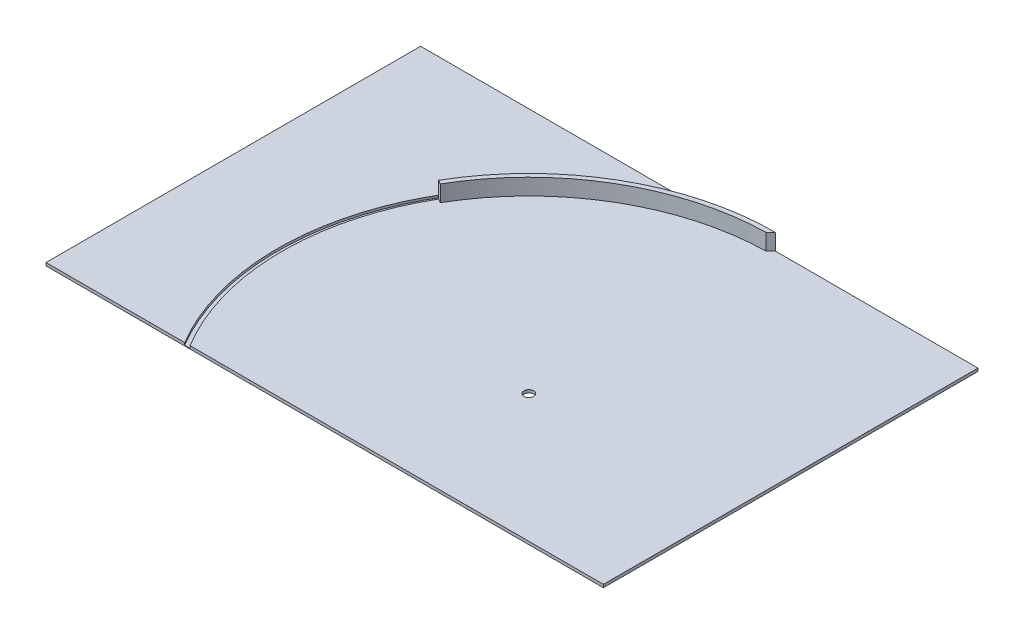
SolidWorks part; units mm, degrees
ref_plane "Front Plane" through (0, 0, 0) normal (0, 0, 1) x (1, 0, 0)
ref_plane "Top Plane" through (0, 0, 0) normal (0, 1, 0) x (1, 0, 0)
ref_plane "Right Plane" through (0, 0, 0) normal (1, 0, 0) x (0, 0, -1)
sketch "Sketch3" plane through (0, 0, 0) normal (0, 1, 0) x (1, 0, 0)
  line L1 (0, 0) -> (-839.8654, 0) construction
  line L2 (0, 0) -> (-451.1992, 260.5) construction
  line L3 (0, 531) -> (0, 521)
  line L4 (-459.8595, 265.5) -> (-451.1992, 260.5)
  circle A0 centre (0, 0) radius 250 construction
  arc A1 (0, 521) -> (-451.1992, 260.5) centre (0, 0) ccw
  arc A2 (0, 531) -> (-459.8595, 265.5) centre (0, 0) ccw
  dimension "D1" = 500
  dimension "D2" = 521
  dimension "D3" = 30
  dimension "D4" = 10
extrude "Boss-Extrude1" add sketch "Sketch3" along normal blind 35
sketch "Sketch4" plane through (0, 0, 0) normal (0, 1, 0) x (1, 0, 0)
  line L1 (-764.07, -275.4) -> (435.93, -275.4)
  line L2 (-764.07, -275.4) -> (-764.07, 531)
  line L3 (-764.07, 531) -> (435.93, 531)
  line L4 (435.93, -275.4) -> (435.93, 531)
  arc A0 (0, 531) -> (-459.8595, 265.5) centre (0, 0) ccw construction
  dimension "D1" = 1200
  dimension "D2" = 275.4
  dimension "D3" = 764.07
extrude "Boss-Extrude2" add sketch "Sketch4" against normal blind 6.35
chamfer "Chamfer1" distance 10 angle 45 1 edges at (0, 17.5, -521)
hole_wizard "Ø20.0mm Dowel Hole1" positions "Sketch6" profile "Sketch7" hole size "Ø20.0" standard "ANSI Metric" end condition through all
sketch "Sketch6" plane through (0, 0, 0) normal (0, 1, 0) x (1, 0, 0)
  point P0 (0, 0)
sketch "Sketch7" plane through (0, 0, 0) normal (1, 0, 0) x (0, 0, 1)
  line L0 (0, 0) -> (0, 6.35)
  line L1 (0, 6.35) -> (10.5, 6.35)
  line L2 (10.5, 6.35) -> (10.5, 0)
  line L5 (10.5, 0) -> (0, 0)
  line L11 (0, -6.35) -> (0, 107.95) construction
  dimension "Thru Hole Dia." = 21
  dimension "Thru Hole Depth" = 6.35
sketch "Sketch8" plane through (0, 0, 0) normal (0, 1, 0) x (1, 0, 0)
  line L1 (0, 531) -> (-764.07, 531) construction
  line L2 (-764.07, -275.4) -> (435.93, -275.4) construction
  line L3 (-462.5497, -280.5864) -> (-453.9998, -275.4)
  line L4 (0, 541) -> (0, 531)
  arc A0 (0, 531) -> (-453.9998, -275.4) centre (0, 0) ccw
  arc A1 (0, 541) -> (-462.5497, -280.5864) centre (0, 0) ccw
  dimension "D1" = 10
extrude "Cut-Extrude1" cut sketch "Sketch8" against normal blind 5
equation "\"D2@Sketch3\"=(\"D1@Sketch3\"/2)+271"
